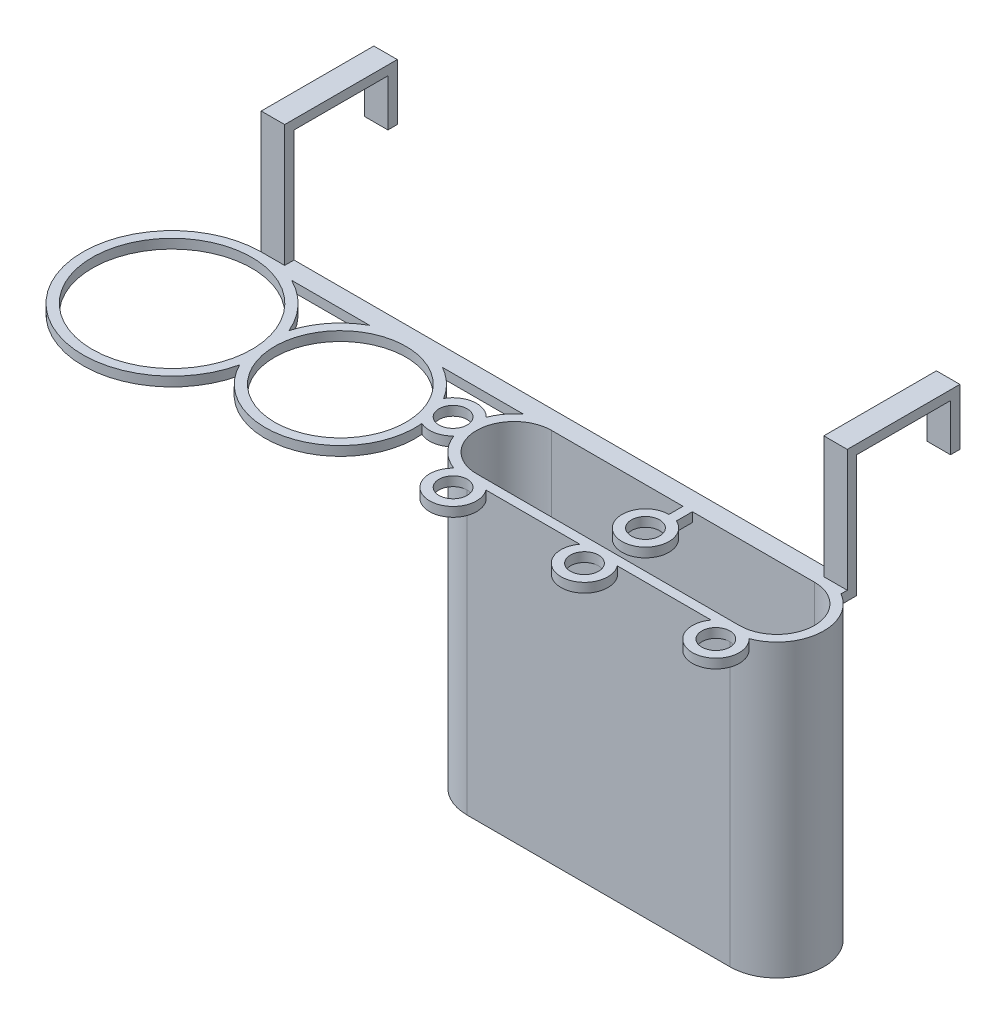
SolidWorks part; units mm, degrees
ref_plane "Front Plane" through (0, 0, 0) normal (0, 0, 1) x (1, 0, 0)
ref_plane "Top Plane" through (0, 0, 0) normal (0, 1, 0) x (1, 0, 0)
ref_plane "Right Plane" through (0, 0, 0) normal (1, 0, 0) x (0, 0, -1)
sketch "Sketch1" plane through (0, 0, 0) normal (0, 1, 0) x (1, 0, 0)
  line L0 (63.8911, 9) -> (91.8911, 9) construction
  line L1 (91.8911, 9) -> (119.8911, 9) construction
  line L2 (63.8911, 9) -> (119.8911, 9) construction
  line L3 (63.8911, 17) -> (119.8911, 17)
  line L4 (63.8911, 1) -> (119.8911, 1)
  line L5 (91.8911, 12) -> (91.8911, 17)
  line L6 (91.8911, 6) -> (91.8911, 1)
  line L7 (102.6516, 17) -> (-39.8619, 17) construction
  line L8 (32.8634, 3) -> (0, 0) construction
  line L9 (32.8634, 3) -> (50.8911, 9) construction
  line L10 (50.8911, 9) -> (63.8911, 9) construction
  circle A0 centre (0, 0) radius 17
  circle A1 centre (32.8634, 3) radius 14
  circle A2 centre (63.8911, 9) radius 8 construction
  circle A3 centre (119.8911, 9) radius 8 construction
  circle A4 centre (91.8911, 9) radius 3
  circle A5 centre (63.8911, -4) radius 3
  circle A6 centre (91.8911, -4) radius 3
  circle A7 centre (119.8911, -4) radius 3
  circle A8 centre (50.8911, 9) radius 3
  arc A9 (63.8911, 17) -> (63.8911, 1) centre (63.8911, 9) ccw
  arc A10 (119.8911, 1) -> (119.8911, 17) centre (119.8911, 9) ccw
  point P19 (18.9213, 1.7273)
  point P20 (16.9296, 1.5455)
  point P21 (46.147, 7.4211)
  point P22 (48.0446, 8.0526)
  point P23 (53.8911, 9)
  point P24 (55.8911, 9)
  point P25 (71.8911, 9)
  point P26 (111.8911, 9)
  point P27 (127.8911, 9)
  point P28 (63.8911, -1)
  point P33 (91.8911, -1)
  point P34 (119.8911, -1)
  point P41 (0, 0)
  point P42 (0, 0)
  dimension "D1" = 6
  dimension "D2" = 16
  dimension "D3" = 28
  dimension "D4" = 34
  dimension "D5" = 2
  dimension "D6" = 2
  dimension "D7" = 2
  dimension "D8" = 40
  dimension "D9" = 2
extrude "Extrude-Thin1" add sketch "Sketch1" along normal blind 2 thin contours A4 | L5 | L3 A10 L4 A9 | A6 | A7 | A5 | A8 | A1 | A0 thin type one direction wall 2
extrude "Extrude-Thin2" add sketch "Sketch1<3>" against normal blind 60 thin contours L3 A10 L4 A9 thin type one direction wall 2
sketch "Sketch1<3>" plane through (0, 0, 0) normal (0, 1, 0) x (1, 0, 0) same geometry as "Sketch1"
sketch "Sketch2" plane through (0, 0, 0) normal (1, 0, 0) x (0, 0, -1)
  line L0 (19, 2) -> (19, 28)
  line L1 (19, 28) -> (43, 28)
  line L2 (43, 28) -> (43, 16)
  line L3 (43, 16) -> (41, 16)
  line L4 (41, 16) -> (41, 26)
  line L5 (41, 26) -> (21, 26)
  line L6 (21, 26) -> (21, 0)
  line L7 (21, 0) -> (19, 0)
  line L8 (19, 0) -> (19, 2)
  dimension "D1" = 2
  dimension "D2" = 2
  dimension "D3" = 2
  dimension "D4" = 2
  dimension "D5" = 26
  dimension "D6" = 10
  dimension "D7" = 20
extrude "Boss-Extrude1" add sketch "Sketch2" along normal blind 5 separate body
extrude "Boss-Extrude2" add sketch "Sketch2<2>" along normal blind 5 from vertex separate body starting at point (119.8911, 2, -19)
sketch "Sketch2<2>" plane through (0, 0, 0) normal (1, 0, 0) x (0, 0, -1) same geometry as "Sketch2"
sketch "Sketch3" plane through (0, 0, 0) normal (-1, 0, 0) x (0, 0, 1)
  line L1 (-21, 0) -> (-17, 0)
  line L2 (-21, 0) -> (-21, 2)
  line L3 (-21, 2) -> (-17, 2)
  line L4 (-17, 0) -> (-17, 2)
extrude "Boss-Extrude3" add sketch "Sketch3" against normal up to surface (124.8911 mm away) up to face at (124.8911, 17.5, -31)
